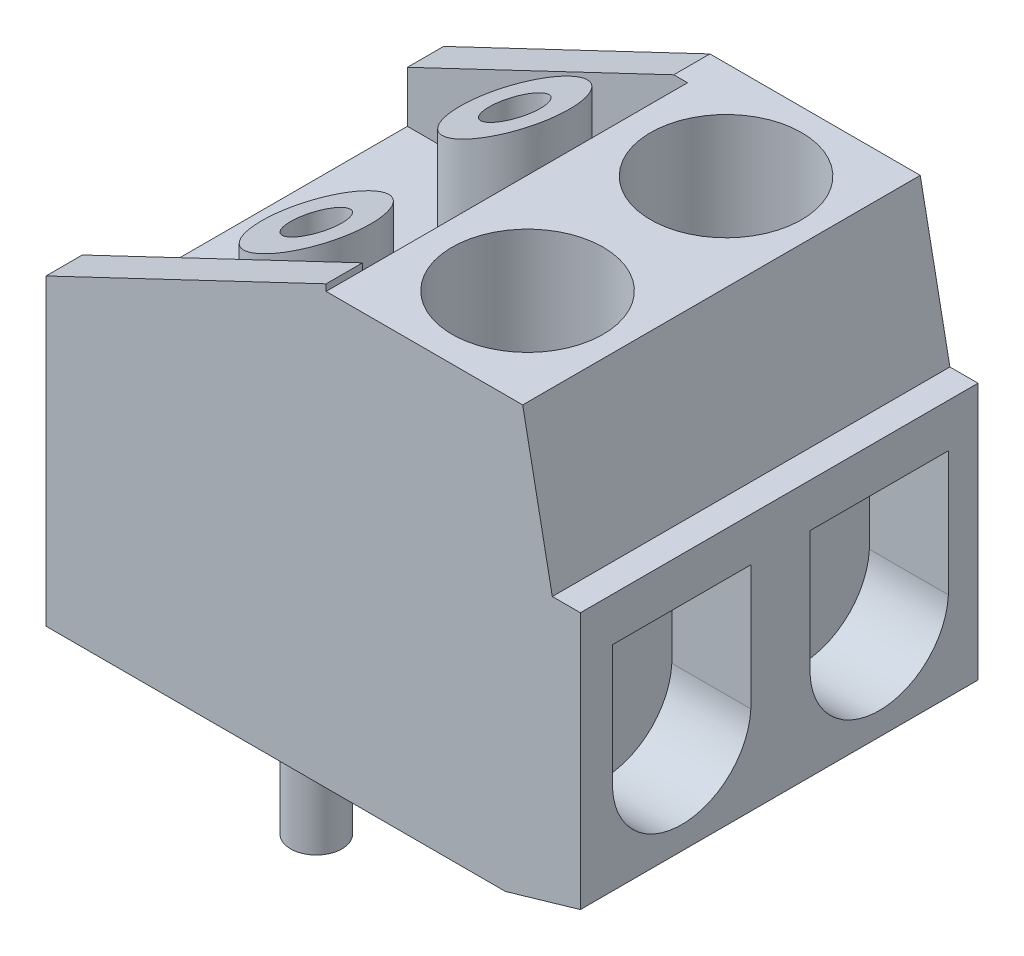
SolidWorks part; units mm, degrees
ref_plane "Front" through (0, 0, 0) normal (0, 0, 1) x (1, 0, 0)
ref_plane "Top" through (0, 0, 0) normal (0, 1, 0) x (1, 0, 0)
ref_plane "Right" through (0, 0, 0) normal (1, 0, 0) x (0, 0, -1)
sketch "Эскиз1" plane through (0, 0, 0) normal (0, 0, 1) x (1, 0, 0)
  line L0 (-89.1672, 0) -> (80.0631, 0) construction
  line L1 (0, 62.2564) -> (0, -61.1853) construction
  line L2 (-9.603, -3.6911) -> (-9.603, 8.7089) construction
  line L3 (-7.0903, 0) -> (-7.0903, 7.6783)
  line L4 (-7.0903, 7.6783) -> (-0.3491, 10.8845)
  line L5 (-0.3491, 10.8845) -> (4.9759, 10.8845)
  line L6 (4.9759, 10.8845) -> (5.7256, 7.059)
  line L7 (5.7256, 7.059) -> (6.4369, 7.059)
  line L8 (6.4369, 7.059) -> (6.4369, 0.5516)
  line L9 (6.4369, 0.5516) -> (4.5383, 0)
  line L10 (4.5383, 0) -> (-7.0903, 0)
  line L11 (4.5383, 5.9531) -> (6.4369, 5.9531) construction
  line L12 (6.4369, 1.1273) -> (4.5383, 1.1273) construction
  point P19 (-2.8456, -3.703)
  dimension "D1" = 12.4
extrude "Бобышка-Вытянуть1" add sketch "Эскиз1" along normal mid plane 15
sketch "Эскиз2" plane through (0, 0, 0) normal (0, 1, 0) x (1, 0, 0)
  line L0 (-7.0532, -9.9119) -> (6.3468, -9.9119) construction
  line L1 (2.5355, 8.3593) -> (2.5355, -8.1809) construction
  line L2 (-9.2375, 5.0247) -> (7.7308, 5.0247) construction
  line L3 (-8.1434, 0) -> (7.2333, 0) construction
  line L4 (-8.1434, -5.0635) -> (7.2333, -5.0635) construction
  line L6 (-7.0903, 6.5843) -> (0, 6.5843)
  line L7 (-7.0903, 6.5843) -> (-7.0903, -6.5088)
  line L8 (-7.0903, -6.5088) -> (0, -6.5088)
  line L9 (0, 6.5843) -> (0, -6.5088)
  circle A0 centre (2.5355, 5.0247) radius 1.9121
  circle A1 centre (2.5355, 0) radius 1.9121
  circle A2 centre (2.5355, -5.0635) radius 1.9121
  circle A3 centre (-2.8126, 5.0247) radius 0.65
  circle A4 centre (-2.8126, 5.0247) radius 1.3809
  circle A5 centre (-2.8126, 0) radius 0.65
  circle A6 centre (-2.8126, 0) radius 1.3809
  circle A7 centre (-2.8126, -5.0635) radius 0.65
  circle A8 centre (-2.8126, -5.0635) radius 1.3809
  dimension "D2" = 13.0931
  dimension "D4" = 1.3
  dimension "D1" = 13.4
  dimension "D3" = 7.0903
extrude "Вырез-Вытянуть1" cut sketch "Эскиз2" against normal blind 4.5 from surface contours A0 | A1 | A2 | L9 L6 L7 L8 A8 A6 A4 | A7 | A5 | A3 region at (-3.5451, 0, -6.4354) region at (2.5355, 0, -5.0247) region at (2.5355, 0, 0) region at (2.5355, 0, 5.0635) region at (-2.8126, 0, -5.0247) region at (-2.8126, 0, 0) region at (-2.8126, 0, 5.0635) starting at face at (2.3134, 10.8845, 0)
sketch "Эскиз3" plane through (6.4369, 0, 0) normal (1, 0, 0) x (0, 0, -1)
  line L0 (1.75, 5.9531) -> (-1.75, 5.9531)
  line L2 (0, 0) -> (0, 7.6783) construction
  line L3 (-1.75, 5.9531) -> (-1.75, 2.7941)
  line L4 (0, 6.2451) -> (0, -0.6569) construction
  line L5 (1.75, 5.9531) -> (1.75, 2.7941)
  line L14 (3.25, 5.9531) -> (3.25, 2.7941)
  line L15 (6.75, 5.9531) -> (3.25, 5.9531)
  line L16 (6.75, 5.9531) -> (6.75, 2.7941)
  line L17 (-6.75, 5.9531) -> (-6.75, 2.7941)
  line L18 (-6.75, 5.9531) -> (-3.25, 5.9531)
  line L19 (-3.25, 5.9531) -> (-3.25, 2.7941)
  arc A0 (-1.75, 2.7941) -> (1.75, 2.7941) centre (0, 2.8837) ccw
  arc A1 (3.25, 2.7941) -> (6.75, 2.7941) centre (5, 2.8837) ccw
  arc A2 (-3.25, 2.7941) -> (-6.75, 2.7941) centre (-5, 2.8837) cw
  point P9 (0, 1.1273)
  point P11 (0, 5.9531)
  dimension "D1" = 1.75
  dimension "D2" = 2
extrude "Вырез-Вытянуть2" cut sketch "Эскиз3" against normal blind 2
extrude "Бобышка-Вытянуть3" add sketch "Эскиз2<6>" against normal blind 3.7 contours A3 | A5 | A7 region at (-2.8126, 0, -5.0247) region at (-2.8126, 0, 0)
sketch "Эскиз2<6>" plane through (0, 0, 0) normal (0, 1, 0) x (1, 0, 0) same geometry as "Эскиз2"
sketch "Эскиз4" plane through (0, 0, 0) normal (1, 0, 0) x (0, 0, -1)
  line L0 (10.0811, 0.0006) -> (10.0811, 10.8006) construction
  line L1 (5.0503, 6.3845) -> (5.0247, 0) construction
  line L2 (0.4648, 6.3814) -> (0.4176, -0.0031) construction
  line L3 (-5.0492, 6.3845) -> (-5.0635, 0) construction
  line L4 (7.117, 4.5486) -> (-7.0734, 4.5486) construction
  line L5 (3.0261, 2.5032) -> (3.0261, 5.8697)
  line L6 (3.0261, 5.8697) -> (2.1312, 5.8697)
  line L7 (2.1312, 5.8697) -> (2.1312, 2.5032)
  line L8 (2.1312, 2.5032) -> (0.4361, 2.5001)
  line L9 (3.0261, 2.5032) -> (6.4139, 2.5032)
  line L10 (6.4139, 2.5032) -> (6.4139, 0.9327)
  line L11 (6.4139, 0.9327) -> (-0.0046, 0.9327)
  line L13 (-1.2588, 2.5282) -> (-1.2588, 0.9514)
  line L14 (-1.2588, 0.9514) -> (0.8536, 0.9264)
  line L18 (-1.2588, 2.5282) -> (0.4361, 2.5001)
  circle A0 centre (5.0429, 4.5486) radius 0.7755
  circle A1 centre (5.0429, 4.5486) radius 1.4112
  circle A2 centre (0, 4.5486) radius 0.7755
  circle A3 centre (0, 4.5486) radius 1.4112
  circle A4 centre (-5.0533, 4.5486) radius 0.7755
  circle A5 centre (-5.0533, 4.5486) radius 1.4112
  dimension "D2" = 3.39
  dimension "D1" = 10.8
extrude "Вырез-Вытянуть3" cut sketch "Эскиз4" along normal blind 1.5 from surface contours A1 A0 | A0 | A3 A2 | A2 | A5 A4 | A4 | L18 L11 L10 L9 L5 L6 L7 L8 region at (0, 2.2132, -2.5772) region at (0, 4.5486, -5.0429) region at (0, 4.5486, -3.6717) region at (0, 4.5486, 0) region at (0, 4.5486, 1.3712) region at (0, 4.5486, 5.0533) region at (0, 4.5486, 6.4246) starting at face at (-7.0903, 5.4353, -0.0189)
sketch "Эскиз5" plane through (0, 10.8845, 0) normal (0, 1, 0) x (1, 0, 0)
  line L0 (-7.0903, -2.5635) -> (6.4369, -2.5635)
  line L1 (-7.0903, 6.5843) -> (-7.0903, -6.5088) construction
  line L2 (6.4369, -7.5) -> (6.4369, 7.5) construction
  line L3 (-7.0903, -2.5635) -> (-7.0903, -7.5)
  line L4 (-7.0903, -7.5) -> (6.4369, -7.5)
  line L5 (6.4369, -7.5) -> (6.4369, -2.5635)
  line L6 (-7.0903, -1.6435) -> (0, -1.6435)
  line L7 (-7.0903, -1.6435) -> (-7.0903, -2.5635)
  line L8 (0, -1.6435) -> (0, -2.5635)
  circle A0 centre (-2.8126, -5.0635) radius 0.65 construction
  circle M3 centre (2.5355, -5.0635) radius 1.9121
  line M5 (0, 6.5843) -> (0, -6.5088)
  line M6 (0, -6.5088) -> (-0.3491, -6.5088)
  line M7 (-0.3491, -6.5088) -> (-0.3491, -7.5)
  line M8 (-0.3491, -7.5) -> (4.9759, -7.5)
  line M9 (4.9759, -7.5) -> (4.9759, 7.5)
  dimension "D1" = 2.5
  dimension "D2" = 0.92
extrude "Вырез-Вытянуть4" cut sketch "Эскиз5" against normal through all contours L3 L4 L0 M7 M6 M5 | L4 L5 L0 M9 | L0 M5 M6 M7 M8 M9 M3 | M3 region at (-3.5788, 10.8845, 5.0121) region at (2.488, 10.8845, 2.6361) region at (5.7064, 10.8845, 5.0318) region at (2.5355, 10.8845, 5.0635)
extrude "Бобышка-Вытянуть4" add sketch "Эскиз5<3>" along normal up to surface (4.666 mm away) from surface contours L6 L7 L0 M5 region at (-3.5451, 10.8845, 2.1035) up to face at (-2.1626, 10.022, 0) starting at face at (-2.8126, 6.3845, -6.4056)
sketch "Эскиз5<3>" plane through (0, 10.8845, 0) normal (0, 1, 0) x (1, 0, 0) same geometry as "Эскиз5"
